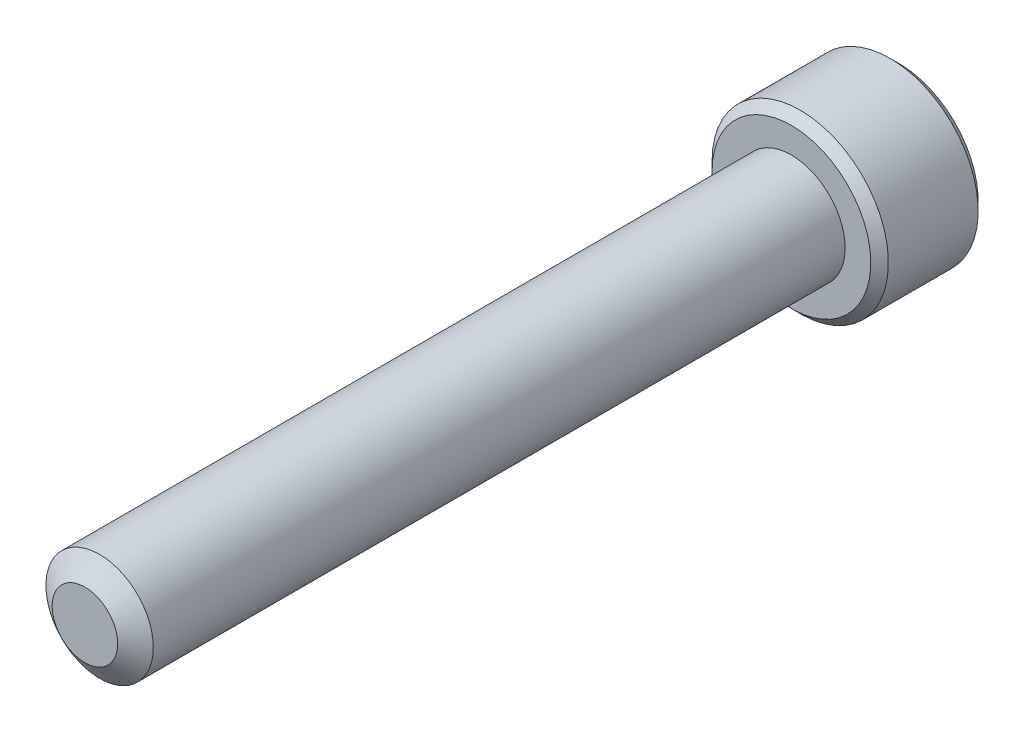
SolidWorks part; units mm, degrees
other "DetailItem1"
ref_plane "Front Plane" through (0, 0, 0) normal (0, 0, 1) x (1, 0, 0)
ref_plane "Top Plane" through (0, 0, 0) normal (0, 1, 0) x (1, 0, 0)
ref_plane "Right Plane" through (0, 0, 0) normal (1, 0, 0) x (0, 0, -1)
sketch "Sketch1" plane through (0, 0, 0) normal (0, 0, 1) x (1, 0, 0)
  circle A0 centre (0, 0) radius 2.413
  dimension "OD" = 4.826
extrude "Extrude1" add sketch "Sketch1" against normal blind 31.75
sketch "Sketch2" plane through (0, 0, 0) normal (0, 0, 1) x (1, 0, 0)
  circle A0 centre (0, 0) radius 2.413 construction
  circle A1 centre (0, 0) radius 2.413
curve "Helix/Spiral1" pitch 1.0583 height 32.8083 turns 31 parameters "pitch"=1.0583
sketch "Sketch3" plane through (0, 0, 0) normal (1, 0, 0) x (0, 0, -1)
  line L0 (-0.926, 2.413) -> (-0.5292, 1.7256)
  line L1 (-0.5292, 1.7256) -> (-0.3969, 1.7256)
  line L2 (-0.3969, 1.7256) -> (0, 2.413)
  line L3 (-0.926, 2.413) -> (0, 2.413)
  line L4 (-0.463, 2.413) -> (-0.463, 1.7256) construction
  line L5 (-0.7276, 2.0693) -> (-0.1984, 2.0693) construction
  line L6 (0, 2.413) -> (0, -2.413) construction
  dimension "D1" = 0.1323
  dimension "D2" = 0.5292
  dimension "D3" = 60
sweep "Cut-Sweep1" [suppressed] cut profiles "Sketch3" path "Helix/Spiral1"
sketch "Sketch4" plane through (0, 0, 0) normal (1, 0, 0) x (0, 0, -1)
  line L0 (0.6592, 2.413) -> (0, 1.4716)
  line L1 (0, 1.4716) -> (0, 2.413)
  line L2 (0.6592, 2.413) -> (0, 2.413)
  line L3 (-0.926, 2.413) -> (0, 2.413) construction
  line L4 (0, 0) -> (7.0209, 0) construction
  dimension "D1" = 55
  dimension "D2" = 0.254
revolve "Cut-Revolve1" cut sketch "Sketch4" angle 360 about L4
sketch "Sketch6" plane through (0, 0, -31.75) normal (0, 0, -1) x (-1, 0, 0)
  circle A0 centre (0, 0) radius 3.9624
  dimension "head dia" = 7.9248
extrude "Extrude2" add sketch "Sketch6" along normal blind 4.826
sketch "Sketch7" plane through (0, 0, -36.576) normal (0, 0, -1) x (-1, 0, 0)
  line L1 (0, 2.2914) -> (-1.9844, 1.1457)
  line L2 (-1.9844, 1.1457) -> (-1.9844, -1.1457)
  line L3 (-1.9844, -1.1457) -> (0, -2.2914)
  line L4 (0, -2.2914) -> (1.9844, -1.1457)
  line L5 (1.9844, -1.1457) -> (1.9844, 1.1457)
  line L6 (1.9844, 1.1457) -> (0, 2.2914)
  circle A0 centre (0, 0) radius 1.9844 construction
  dimension "hex dia" = 3.9688
extrude "Cut-Extrude1" cut sketch "Sketch7" against normal blind 2.9766
sketch "Sketch8" plane through (0, 0, -36.576) normal (0, 0, -1) x (-1, 0, 0)
  circle A0 centre (0, 0) radius 2.2914
extrude "Cut-Extrude2" cut sketch "Sketch8" against normal through all draft 45
chamfer "Chamfer1" distance 0.3962 angle 45 2 edges at (-3.9624, 0, -36.576) (-3.9624, 0, -31.75)
sketch "Sketch10" plane through (0, 0, -31.75) normal (0, 0, 1) x (1, 0, 0)
  circle A0 centre (0, 0) radius 2.413
extrude "Partial Thread" [suppressed] add sketch "Sketch10" along normal offset from surface (19.05 mm away) 2.54 up to face at (1.4716, 0, 0)
sketch "Sketch9" plane through (0, 0, 0) normal (1, 0, 0) x (0, 0, -1)
  line L0 (0, 2.413) -> (0, -2.413) construction
  line L1 (1.5875, 2.413) -> (1.5875, -2.413) construction
  dimension "D1" = 1.5875
equation "\"D3@Helix/Spiral1\" = \"screw length@Extrude1\"+\"pitch@Helix/Spiral1\""
equation "\"D1@Sketch3\" = \"pitch@Helix/Spiral1\"*.125"
equation "\"D2@Sketch3\" = \"pitch@Helix/Spiral1\"*.5"
equation "\"D1@Cut-Extrude1\" = \"hex dia@Sketch7\"*.75"
equation "\"D1@Chamfer1\" = \"head dia@Sketch6\"*.05"
equation "\"D1@Sketch9\" = \"pitch@Helix/Spiral1\"*1.5"
